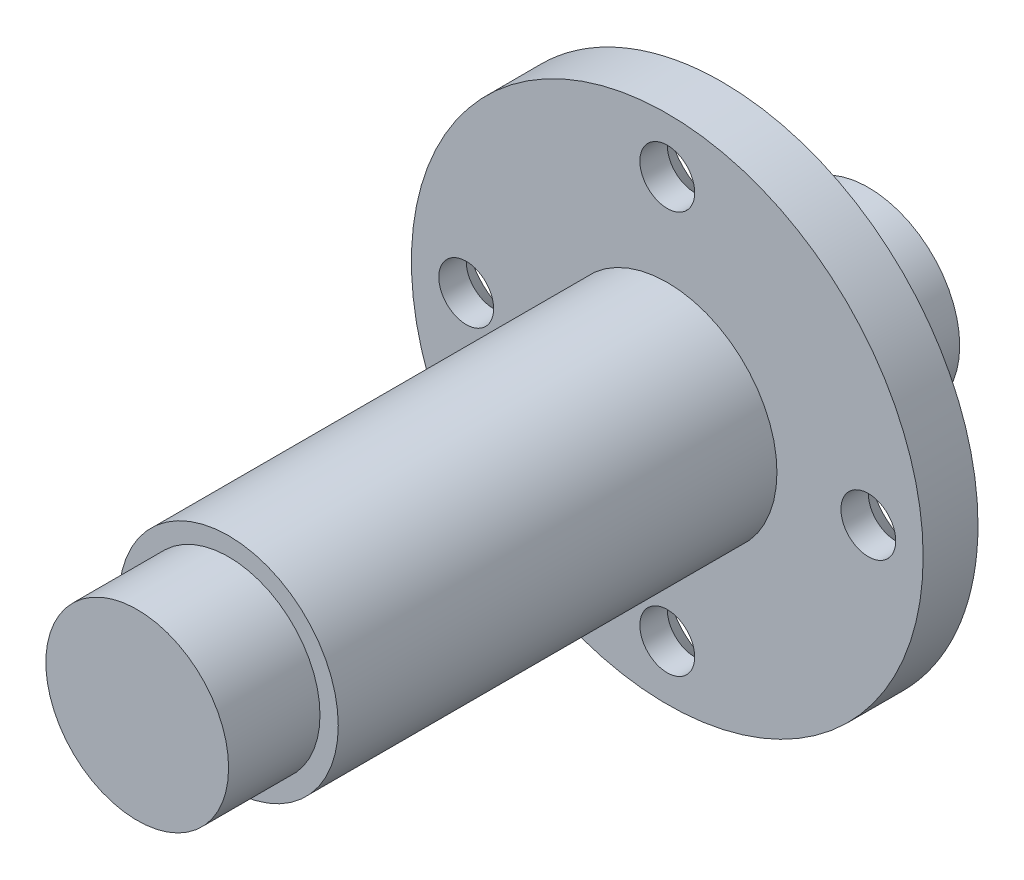
SolidWorks part; units mm, degrees
ref_plane "Alzado" through (0, 0, 0) normal (0, 0, 1) x (1, 0, 0)
ref_plane "Planta" through (0, 0, 0) normal (0, 1, 0) x (1, 0, 0)
ref_plane "Vista lateral" through (0, 0, 0) normal (1, 0, 0) x (0, 0, -1)
sketch "Croquis1" plane through (0, 0, 0) normal (0, 0, 1) x (1, 0, 0)
  circle A0 centre (0, 0) radius 5
  dimension "D1" = 10
extrude "Saliente-Extruir1" add sketch "Croquis1" along normal blind 5
sketch "Croquis2" plane through (0, 0, 5) normal (0, 0, 1) x (1, 0, 0)
  circle A0 centre (0, 0) radius 7
  dimension "D1" = 14
extrude "Saliente-Extruir2" add sketch "Croquis2" along normal blind 3
sketch "Croquis3" plane through (0, 0, 8) normal (0, 0, 1) x (1, 0, 0)
  circle A0 centre (0, 0) radius 14
  dimension "D1" = 28
extrude "Saliente-Extruir3" add sketch "Croquis3" along normal blind 3
sketch "Croquis4" plane through (0, 0, 11) normal (0, 0, 1) x (1, 0, 0)
  circle A0 centre (0, 0) radius 6
  dimension "D1" = 12
extrude "Saliente-Extruir4" add sketch "Croquis4" along normal blind 24
sketch "Croquis5" plane through (0, 0, 35) normal (0, 0, 1) x (1, 0, 0)
  circle A0 centre (0, 0) radius 5
  dimension "D1" = 10
extrude "Saliente-Extruir5" add sketch "Croquis5" along normal blind 5
sketch "Croquis6" plane through (0, 0, 8) normal (0, 0, -1) x (-1, 0, 0)
  line L0 (0, 0) -> (11, 0) construction
  circle A0 centre (0, 0) radius 11 construction
  circle A1 centre (11, 0) radius 1.5
  circle A2 centre (0, -11) radius 1.5
  circle A3 centre (-11, 0) radius 1.5
  circle A4 centre (0, 11) radius 1.5
  point P14 (0, 0)
  dimension "D1" = 22
  dimension "D2" = 3
  dimension "D3" = 4
extrude "Cortar-Extruir1" cut sketch "Croquis6" against normal blind 5
chamfer "Chaflán1" distance 1.5 angle 45 4 edges at (-1.5, -11, 8) (-12.5, 0, 8) (-1.5, 11, 8) (9.5, 0, 8)
